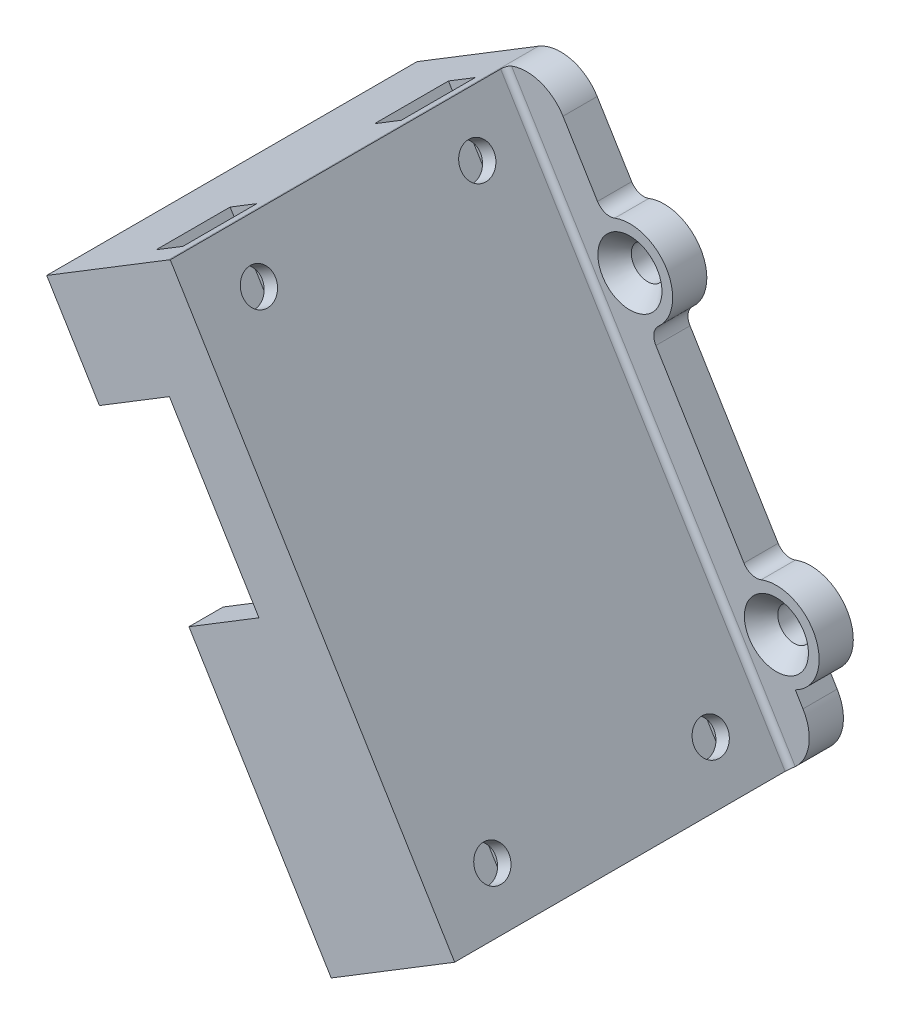
SolidWorks part; units mm, degrees
ref_plane "Front Plane" through (0, 0, 0) normal (0, 0, 1) x (1, 0, 0)
ref_plane "Top Plane" through (0, 0, 0) normal (0, 1, 0) x (1, 0, 0)
ref_plane "Right Plane" through (0, 0, 0) normal (1, 0, 0) x (0, 0, -1)
sketch "Sketch2" plane through (0, 0, 0) normal (0, 0, 1) x (1, 0, 0)
  line L0 (-38.8523, 46.0124) -> (-20.099, 15.2827)
  line L1 (-20.099, 15.2827) -> (-3.027, 25.7013)
  line L2 (-3.027, 25.7013) -> (-21.7803, 56.4309)
  line L3 (-21.7803, 56.4309) -> (-38.8523, 46.0124)
  line L4 (-47.5806, 48.1249) -> (-22.2115, 6.5545)
  line L5 (-22.2115, 6.5545) -> (5.7013, 23.5888)
  line L6 (5.7013, 23.5888) -> (-19.6678, 65.1592)
  line L7 (-19.6678, 65.1592) -> (-47.5806, 48.1249)
  dimension "D1" = 6.35
extrude "Boss-Extrude1" add sketch "Sketch2" along normal blind 3.048
sketch "Sketch3" plane through (0, 0, 3.048) normal (0, 0, 1) x (1, 0, 0)
  line L0 (-38.8523, 46.0124) -> (-20.099, 15.2827)
  line L1 (-20.099, 15.2827) -> (-3.027, 25.7013)
  line L2 (-3.027, 25.7013) -> (-21.7803, 56.4309)
  line L3 (-21.7803, 56.4309) -> (-38.8523, 46.0124)
  line L4 (2.4491, 21.6041) -> (-22.92, 63.1745)
  line L5 (-44.3284, 50.1096) -> (-18.9593, 8.5392)
  line L6 (-44.3284, 50.1096) -> (-22.92, 63.1745)
  line L8 (-41.0205, 44.6893) -> (-22.2671, 13.9596) construction
  line L9 (-0.8588, 27.0244) -> (-19.6122, 57.7541) construction
  line L10 (-18.9593, 8.5392) -> (2.4491, 21.6041)
  point P17 (-33.6242, 56.642)
  point P20 (-8.2551, 15.0716)
  dimension "D1" = 2.54
extrude "Boss-Extrude2" add sketch "Sketch3" along normal blind 29.972
sketch "Sketch4" plane through (0, 0, 33.02) normal (0, 0, 1) x (1, 0, 0)
  line L0 (-38.8523, 46.0124) -> (-37.4613, 43.733)
  line L1 (-38.8523, 46.0124) -> (-20.099, 15.2827) construction
  line L2 (-37.4613, 43.733) -> (-20.3893, 54.1516)
  line L3 (-3.027, 25.7013) -> (-21.7803, 56.4309) construction
  line L4 (-20.3893, 54.1516) -> (-21.7803, 56.4309)
  line L5 (-21.7803, 56.4309) -> (-38.8523, 46.0124)
  line L6 (-29.4757, 30.6476) -> (-12.4036, 41.0661)
  line L7 (-12.4036, 41.0661) -> (-3.027, 25.7013)
  line L8 (-3.027, 25.7013) -> (-20.099, 15.2827)
  line L9 (-20.099, 15.2827) -> (-29.4757, 30.6476)
extrude "Boss-Extrude3" add sketch "Sketch4" against normal blind 3.048
sketch "Sketch12" plane through (0, 0, 3.048) normal (0, 0, 1) x (1, 0, 0)
  line L0 (2.4491, 21.6041) -> (5.7013, 23.5888)
  line L1 (5.7013, 23.5888) -> (8.1204, 25.0651)
  line L2 (8.1204, 25.0651) -> (-17.2487, 66.6355)
  line L3 (-17.2487, 66.6355) -> (-22.92, 63.1745)
  line L4 (-22.92, 63.1745) -> (2.4491, 21.6041)
extrude "Boss-Extrude4" add sketch "Sketch12" against normal blind 3.048
sketch "Sketch13" plane through (11.391, 6.9516, 0) normal (0.8536, 0.5209, 0) x (0, 0, -1)
  line L1 (-33.02, 65.8655) -> (-3.048, 65.8655)
  line L2 (-33.02, 65.8655) -> (-33.02, 17.1655)
  line L3 (-33.02, 17.1655) -> (-3.048, 17.1655)
  line L4 (-3.048, 65.8655) -> (-3.048, 17.1655)
extrude "Boss-Extrude5" add sketch "Sketch13" along normal blind 3.048
hole_wizard "CSK for #4 Flat Head Machine Screw (100)2" positions "Sketch10" profile "Sketch11" countersink size "#4" standard "ANSI Inch" end condition through all
sketch "Sketch10" plane through (-10.0173, -6.1133, 0) normal (-0.8536, -0.5209, 0) x (0, 0, 1)
  point P0 (27.3976, 61.4714)
  point P2 (7.9259, 61.4714)
  point P4 (7.9259, 21.5155)
  point P6 (27.3976, 21.5155)
sketch "Sketch11" plane through (-42.0394, 46.3589, 27.3976) normal (0, 0, 1) x (0.5209, -0.8536, 0)
  line L0 (0, 0) -> (0, 53.3792)
  line L1 (0, 53.3792) -> (1.4732, 53.3792)
  line L2 (1.4732, 53.3792) -> (1.4732, 1.1616)
  line L3 (1.4732, 1.1616) -> (2.8575, 0)
  line L5 (2.8575, 0) -> (0, 0)
  line L6 (-1.4732, 1.1616) -> (-2.8575, 0) construction
  line L11 (0, -6.35) -> (0, 107.95) construction
  dimension "Thru Hole Dia." = 2.9464
  dimension "Thru Hole Depth" = 53.3792
  dimension "Near C'Sink Dia." = 5.715
  dimension "Near C'Sink Angle" = 100
ref_plane "Plane1" through (11.6078, 7.0839, 0) normal (0.8536, 0.5209, 0) x (0, 0, -1)
sketch "Sketch14" plane through (11.6078, 7.0839, 0) normal (0.8536, 0.5209, 0) x (0, 0, -1)
  line L0 (-30.6972, 19.6105) -> (-30.6972, 14.9798)
  line L1 (-27.3976, 57.6614) -> (-24.0981, 59.5664)
  line L2 (-24.0981, 59.5664) -> (-24.0981, 63.3764)
  line L5 (-30.6972, 63.3764) -> (-30.6972, 59.5664)
  line L6 (-30.6972, 59.5664) -> (-27.3976, 57.6614)
  line L7 (-7.9259, 57.6614) -> (-4.6264, 59.5664)
  line L8 (-4.6264, 59.5664) -> (-4.6264, 63.3764)
  line L11 (-11.2255, 63.3764) -> (-11.2255, 59.5664)
  line L12 (-11.2255, 59.5664) -> (-7.9259, 57.6614)
  line L13 (-7.9259, 25.3255) -> (-11.2255, 23.4205)
  line L14 (-11.2255, 23.4205) -> (-11.2255, 19.6105)
  line L17 (-4.6264, 19.6105) -> (-4.6264, 23.4205)
  line L18 (-4.6264, 23.4205) -> (-7.9259, 25.3255)
  line L19 (-27.3976, 25.3255) -> (-30.6972, 23.4205)
  line L20 (-30.6972, 23.4205) -> (-30.6972, 19.6105)
  line L23 (-24.0981, 19.6105) -> (-24.0981, 23.4205)
  line L24 (-24.0981, 23.4205) -> (-27.3976, 25.3255)
  line L25 (-30.6972, 14.9798) -> (-24.0981, 14.9798)
  line L26 (-24.0981, 14.9798) -> (-24.0981, 19.6105)
  line L27 (-11.2255, 19.6105) -> (-11.2255, 14.9798)
  line L28 (-11.2255, 14.9798) -> (-4.6264, 14.9798)
  line L29 (-4.6264, 14.9798) -> (-4.6264, 19.6105)
  line L30 (-4.6264, 63.3764) -> (-4.6264, 70.9964)
  line L31 (-4.6264, 70.9964) -> (-11.2255, 70.9964)
  line L32 (-11.2255, 70.9964) -> (-11.2255, 63.3764)
  line L33 (-24.0981, 63.3764) -> (-24.0981, 70.9964)
  line L34 (-24.0981, 70.9964) -> (-30.6972, 70.9964)
  line L35 (-30.6972, 70.9964) -> (-30.6972, 63.3764)
  line L37 (-27.3976, 65.2814) -> (-29.0474, 64.3289) [skipped]
  line L38 (-25.7478, 64.3289) -> (-27.3976, 65.2814) [skipped]
  line L39 (-6.2761, 64.3289) -> (-7.9259, 65.2814) [skipped]
  line L40 (-7.9259, 65.2814) -> (-9.5757, 64.3289) [skipped]
  line L41 (-9.5757, 18.658) -> (-7.9259, 17.7055) [skipped]
  line L42 (-6.2761, 18.658) -> (-4.6264, 19.6105) [skipped]
  line L43 (-30.6972, 19.6105) -> (-29.0474, 18.658) [skipped]
  line L44 (-25.7478, 18.658) -> (-24.0981, 19.6105) [skipped]
  arc A4 (-30.6972, 61.4714) -> (-24.0981, 61.4714) centre (-27.3976, 61.4714) ccw construction
  arc A5 (-11.2255, 61.4714) -> (-4.6264, 61.4714) centre (-7.9259, 61.4714) ccw construction
  arc A6 (-4.6264, 21.5155) -> (-11.2255, 21.5155) centre (-7.9259, 21.5155) ccw construction
  arc A7 (-24.0981, 21.5155) -> (-30.6972, 21.5155) centre (-27.3976, 21.5155) ccw construction
extrude "Cut-Extrude1" cut sketch "Sketch14" against normal blind 1.397 and the other way blind 1.397
sketch "Sketch15" plane through (0, 0, 0) normal (0, 0, -1) x (-1, 0, 0)
  line L0 (-8.1204, 25.0651) -> (17.2487, 66.6355) construction
  line L1 (47.5806, 48.1249) -> (22.2115, 6.5545) construction
  circle A0 centre (9.7581, 54.3612) radius 9.184
  circle A1 centre (39.9278, 35.5849) radius 8.1247
  circle A2 centre (25.6104, 18.0464) radius 8.2015
  circle A3 centre (-3.4576, 32.7057) radius 5.8102
extrude "Boss-Extrude6" add sketch "Sketch15" against normal blind 3.048
hole_wizard "CSK for #4 Flat Head Machine Screw1" positions "Sketch18" profile "Sketch19" countersink size "#4" standard "ANSI Inch" end condition through all
sketch "Sketch18" plane through (0, 0, 3.048) normal (0, 0, 1) x (1, 0, 0)
  point P0 (3.7644, 32.8603)
  point P2 (-26.4116, 14.2104)
  point P4 (-39.8451, 35.7872)
  point P6 (-9.297, 54.2582)
sketch "Sketch19" plane through (3.7644, 32.8603, 3.048) normal (1, 0, 0) x (0, -1, 0)
  line L0 (0, 0) -> (0, 3.048)
  line L1 (0, 3.048) -> (1.4732, 3.048)
  line L2 (1.4732, 3.048) -> (1.4732, 1.5925)
  line L3 (1.4732, 1.5925) -> (2.8575, 0)
  line L5 (2.8575, 0) -> (0, 0)
  line L6 (-1.4732, 1.5925) -> (-2.8575, 0) construction
  line L11 (0, -6.35) -> (0, 107.95) construction
  dimension "Thru Hole Dia." = 2.9464
  dimension "Thru Hole Depth" = 3.048
  dimension "Near C'Sink Dia." = 5.715
  dimension "Near C'Sink Angle" = 82
sketch "Sketch20" plane through (0, 0, 0) normal (0, 0, -1) x (-1, 0, 0)
  line L0 (14.5423, 62.2008) -> (11.564, 57.3204)
  line L1 (21.7803, 56.4309) -> (38.8523, 46.0124)
  line L2 (38.8523, 46.0124) -> (20.099, 15.2827)
  line L3 (20.099, 15.2827) -> (3.027, 25.7013)
  line L4 (3.027, 25.7013) -> (21.7803, 56.4309)
  line L5 (14.5423, 62.2008) -> (14.5423, 65.1603)
  line L6 (14.5423, 65.1603) -> (8.559, 68.8117)
  line L7 (8.559, 68.8117) -> (-14.062, 31.7445)
  line L8 (-14.062, 31.7445) -> (-6.7627, 27.29)
  line L9 (-8.1204, 25.0651) -> (-6.4843, 27.7461) construction
  line L10 (-6.7627, 27.29) -> (-6.4843, 27.7461)
  line L11 (22.2115, 6.5545) -> (24.782, 10.7665)
  line L12 (47.5806, 48.1249) -> (51.8017, 35.7872)
  line L13 (51.8017, 35.7872) -> (47.5768, 5.2277)
  line L14 (47.5768, 5.2277) -> (22.2115, 6.5545)
  line L15 (7.6103, 50.8419) -> (-1.4954, 35.921)
  line L16 (-5.4488, 29.4429) -> (-6.4843, 27.7461)
  line L17 (28.7292, 17.2345) -> (38.0127, 32.4468)
  line L18 (41.9779, 38.9443) -> (47.5806, 48.1249)
  arc A0 (-1.4954, 35.921) -> (-5.4488, 29.4429) centre (-3.7644, 32.8603) ccw
  arc A1 (11.564, 57.3204) -> (7.6103, 50.8419) centre (9.297, 54.2582) ccw
  arc A2 (38.0127, 32.4468) -> (41.9779, 38.9443) centre (39.8451, 35.7872) ccw
  arc A3 (24.782, 10.7665) -> (28.7292, 17.2345) centre (26.4116, 14.2104) ccw
  circle A4 centre (0, 0) radius 69.342 construction
extrude "Cut-Extrude2" cut sketch "Sketch20" against normal blind 3.048
fillet "Fillet3" radius 3.81 4 edges at (-17.2487, 66.6355, 1.524) (-47.5806, 48.1249, 1.524) (-22.2115, 6.5545, 1.524) (8.1204, 25.0651, 1.524)
fillet "Fillet4" radius 1.27 7 edges at (-24.782, 10.7665, 1.524) (-28.7292, 17.2345, 1.524) (-38.0127, 32.4468, 1.524) (-41.9779, 38.9443, 1.524) (-11.564, 57.3204, 1.524) (-7.6103, 50.8419, 1.524) (1.4954, 35.921, 1.524)
sketch "Sketch21" plane through (-8.9419, 14.6525, 0) normal (0.5209, -0.8536, 0) x (0.8536, 0.5209, 0)
  line L0 (-11.7353, 33.02) -> (16.1787, 33.02) construction
  line L1 (2.2217, 33.02) -> (2.2217, 0) construction
  line L2 (-11.7353, 0) -> (16.1787, 0) construction
  line L4 (0.9517, 33.02) -> (3.4917, 33.02)
  line L5 (0.9517, 33.02) -> (0.9517, 0)
  line L6 (0.9517, 0) -> (3.4917, 0)
  line L7 (3.4917, 33.02) -> (3.4917, 0)
  line L8 (0.9517, 33.02) -> (3.4917, 0) construction
  line L9 (0.9517, 0) -> (3.4917, 33.02) construction
  point P8 (2.2217, 16.51)
  dimension "D1" = 2.54
extrude "Cut-Extrude3" cut sketch "Sketch21" against normal blind 77.47
fillet "Fillet5" radius 0.508 1 edges at (-31.6438, 29.3244, 3.048)
fillet "Fillet6" radius 0.508 1 edges at (-7.6337, 43.977, 3.048)
ref_plane "Plane2" through (2.068, 1.262, 0) normal (0.8536, 0.5209, 0) x (0, 0, -1)
sketch "Sketch22" plane through (2.068, 1.262, 0) normal (0.8536, 0.5209, 0) x (0, 0, -1)
  line L1 (-104.2124, 141.8108) -> (18.8373, 141.8108)
  line L2 (-104.2124, 141.8108) -> (-104.2124, 7.0976)
  line L3 (-104.2124, 7.0976) -> (18.8373, 7.0976)
  line L4 (18.8373, 141.8108) -> (18.8373, 7.0976)
  line L5 (-104.2124, 141.8108) -> (18.8373, 7.0976) construction
  line L6 (-104.2124, 7.0976) -> (18.8373, 141.8108) construction
  point P0 (-42.6876, 74.4542)
extrude "Cut-Extrude4" cut sketch "Sketch22" against normal blind 77.47
